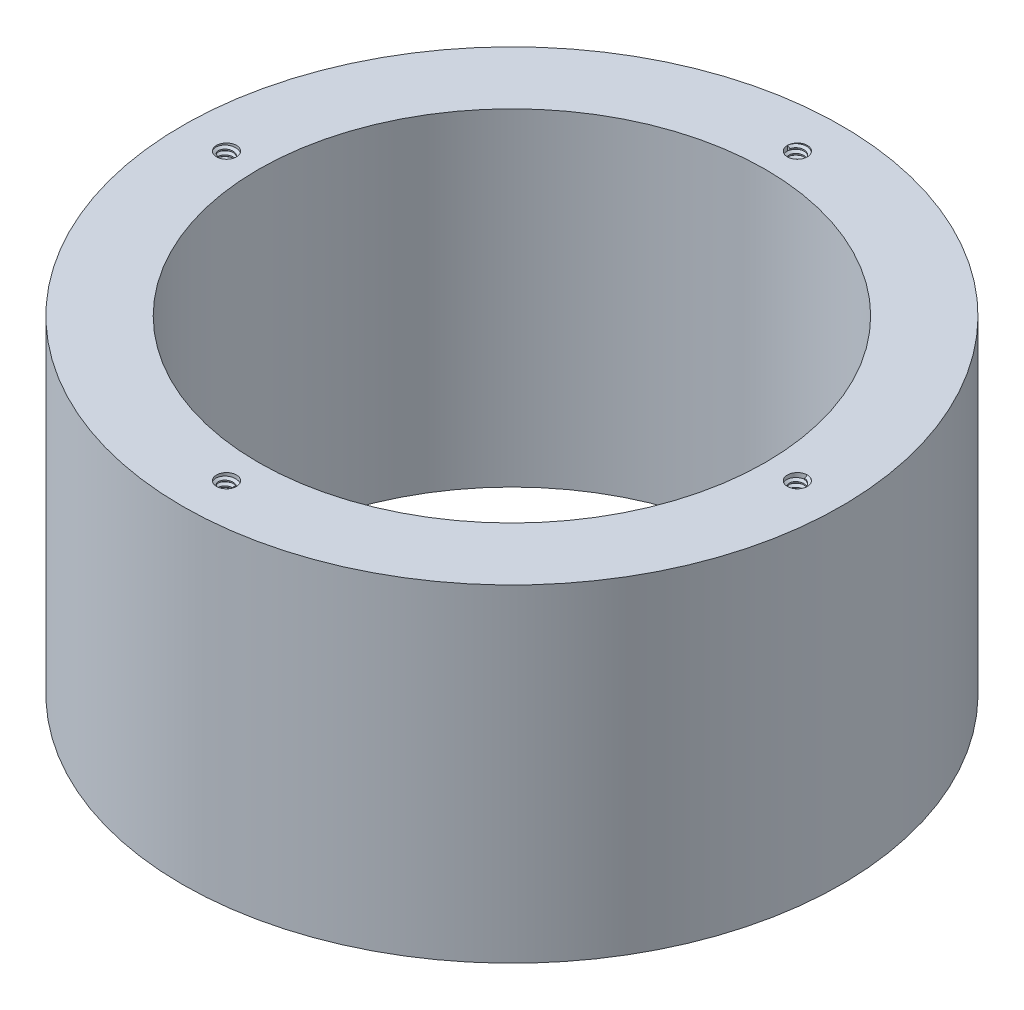
SolidWorks part; units mm, degrees
material "1060 Alloy"
ref_plane "Front Plane" through (0, 0, 0) normal (0, 0, 1) x (1, 0, 0)
ref_plane "Top Plane" through (0, 0, 0) normal (0, 1, 0) x (1, 0, 0)
ref_plane "Right Plane" through (0, 0, 0) normal (1, 0, 0) x (0, 0, -1)
sketch "Sketch1" plane through (0, 0, 0) normal (0, 1, 0) x (1, 0, 0)
  circle A0 centre (0, 0) radius 12.7
  circle A1 centre (0, 0) radius 16.5
  dimension "D1" = 25.4
  dimension "D2" = 33
extrude "Boss-Extrude1" add sketch "Sketch1" along normal blind 16.4
sketch "Sketch2" plane through (0, 16.4, 0) normal (0, 1, 0) x (1, 0, 0)
  circle A0 centre (0, 14.29) radius 0.5
  dimension "D1" = 1
  dimension "D2" = 14.29
extrude "Cut-Extrude1" cut sketch "Sketch2" against normal blind 2
thread "Thread1" pitch 0.25 method extrude profile "Thread Profile2" start angle 0, offset 0, length 2, pitch 0.25, diameter 1
ref_plane "Plane2" through (-0.5, 16.4, -14.29) normal (0, 0, 1) x (-1, 0, 0)
sketch "Thread Profile2" plane through (-0.5, 16.4, -14.29) normal (0, 0, 1) x (-1, 0, 0)
  line L0 (0, 0) -> (0, 0.25) construction
  line L11 (0, 0) -> (0, 0.2187)
  line L12 (0, 0.2187) -> (-0.1353, 0.1406)
  line L13 (-0.1353, 0.1406) -> (-0.1353, 0.0781)
  line L15 (-0.1353, 0.0781) -> (0, 0)
  line L17 (-0.1353, 0.1094) -> (0, 0.1094) construction
  point P2 (0, 0)
  dimension "Pitch" = 0.25
  dimension "Profile_Angle" = 60
  dimension "Profile_Land" = 0.0625
  dimension "Profile_Height" = 0.1353
pattern_circular "CirPattern1" count 4 over 360 about axis through (0, 16.4, 0) along (0, 1, 0) of "Cut-Extrude1", "Thread1"
sketch "Sketch7" plane through (0, 0, 0) normal (0, -1, 0) x (1, 0, 0)
  circle A0 centre (0, 14.29) radius 0.5
  dimension "D1" = 1
  dimension "D2" = 14.29
extrude "Cut-Extrude2" cut sketch "Sketch7" against normal blind 2
thread "Thread2" pitch 0.25 method extrude profile "Thread Profile3" start angle 0, offset 0, length 2, pitch 0.25, diameter 1
ref_plane "Plane3" through (0.5, 0, 14.29) normal (0, 0, 1) x (1, 0, 0)
sketch "Thread Profile3" plane through (0.5, 0, 14.29) normal (0, 0, 1) x (1, 0, 0)
  line L0 (0, 0) -> (0, 0.25) construction
  line L11 (0, 0) -> (0, 0.2187)
  line L12 (0, 0.2187) -> (-0.1353, 0.1406)
  line L13 (-0.1353, 0.1406) -> (-0.1353, 0.0781)
  line L15 (-0.1353, 0.0781) -> (0, 0)
  line L17 (-0.1353, 0.1094) -> (0, 0.1094) construction
  point P2 (0, 0)
  dimension "Pitch" = 0.25
  dimension "Profile_Angle" = 60
  dimension "Profile_Land" = 0.0625
  dimension "Profile_Height" = 0.1353
pattern_circular "CirPattern2" count 4 over 360 about axis through (0, 0, 0) along (0, 1, 0) of "Thread2", "Cut-Extrude2"
